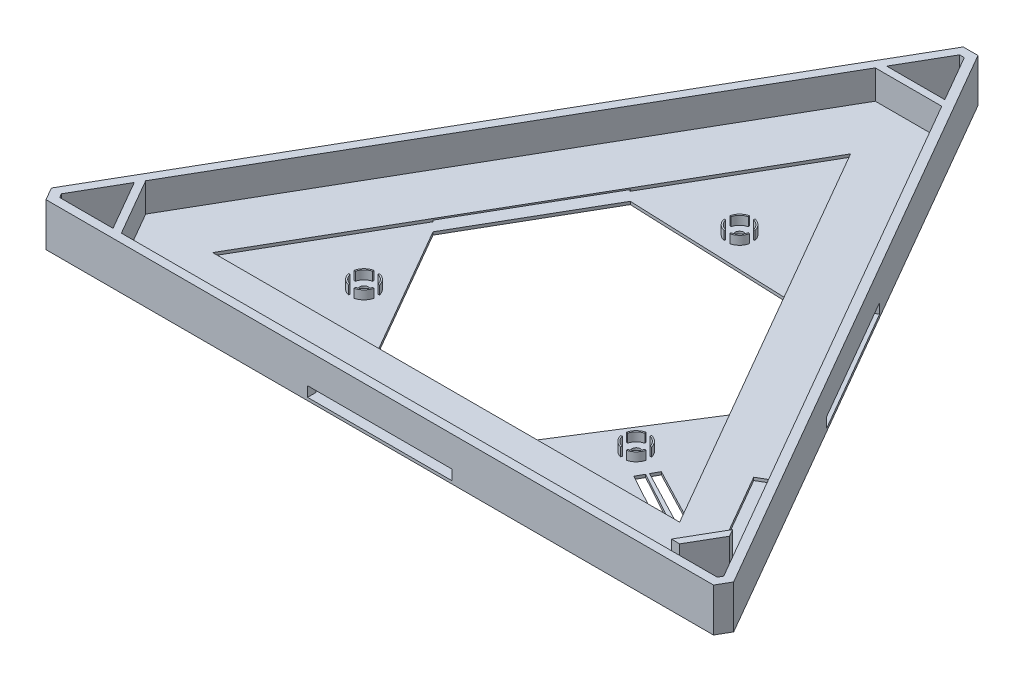
SolidWorks part; units mm, degrees
ref_plane "Front Plane" through (0, 0, 0) normal (0, 0, 1) x (1, 0, 0)
ref_plane "Top Plane" through (0, 0, 0) normal (0, 1, 0) x (1, 0, 0)
ref_plane "Right Plane" through (0, 0, 0) normal (1, 0, 0) x (0, 0, -1)
sketch "Sketch1" plane through (0, 0, 0) normal (0, 1, 0) x (1, 0, 0)
  line L0 (351.2729, 67.6655) -> (468.273, -134.9846)
  line L1 (347.2728, 67.6655) -> (347.2728, 65.1655) construction
  line L2 (409.773, -33.6595) -> (407.6079, -34.9095) construction
  line L3 (468.273, -134.9846) -> (464.2732, -141.9124)
  line L4 (230.2733, -141.9124) -> (464.2732, -141.9124)
  line L5 (230.2733, -141.9124) -> (226.2727, -134.9842)
  line L6 (226.2727, -134.9842) -> (343.2728, 67.6655)
  line L7 (353.4142, 63.9567) -> (351.2491, 62.7067) construction
  line L8 (347.2733, -141.9124) -> (347.2733, -139.4124) construction
  line L9 (231.7167, -139.4124) -> (462.8299, -139.4124)
  line L10 (284.7727, -33.6594) -> (286.9378, -34.9094) construction
  line L11 (344.7161, 65.1655) -> (349.8295, 65.1655)
  line L12 (465.3862, -134.9846) -> (349.8295, 65.1655)
  line L13 (466.2731, -138.4485) -> (464.1081, -137.1985) construction
  line L14 (462.8299, -139.4124) -> (465.3862, -134.9846)
  line L15 (229.1594, -134.9842) -> (344.7161, 65.1655)
  line L16 (229.1594, -134.9842) -> (231.7167, -139.4124)
  line L17 (286.9378, -34.9094) -> (287.3708, -35.1594) construction
  line L18 (230.438, -137.1983) -> (230.871, -136.9483) construction
  line L19 (232.0053, -138.9123) -> (229.7368, -134.9842)
  line L20 (343.2728, 67.6655) -> (351.2729, 67.6655)
  line L21 (345.0048, 64.6655) -> (229.7368, -134.9842)
  line L22 (349.5409, 64.6655) -> (345.0048, 64.6655)
  line L23 (249.0568, -126.4468) -> (246.8918, -127.697) construction
  line L24 (407.6079, -34.9095) -> (407.1749, -35.1595) construction
  line L26 (233.4463, -136.4089) -> (251.9226, -136.4093)
  line L27 (464.8089, -134.9846) -> (462.5412, -138.9123)
  line L28 (462.5412, -138.9123) -> (232.0053, -138.9123)
  line L29 (251.9226, -136.4093) -> (241.8609, -118.9847)
  line L30 (241.8609, -118.9847) -> (232.6236, -134.9842)
  line L31 (232.6236, -134.9842) -> (233.4463, -136.4089)
  line L33 (287.3708, -35.1594) -> (289.5359, -36.4094) construction
  line L34 (254.8093, -136.4089) -> (243.3042, -116.4848)
  line L35 (335.7675, 43.666) -> (243.3042, -116.4848)
  line L36 (358.7782, 43.666) -> (335.7675, 43.666)
  line L38 (289.5359, -36.4094) -> (306.8564, -46.4094) construction
  line L41 (461.939, -134.9846) -> (461.1164, -136.4093)
  line L42 (347.2688, -136.4172) -> (347.2688, -116.4172) construction
  line L43 (442.6021, -136.4093) -> (452.6999, -118.9847)
  line L44 (245.2636, -119.878) -> (249.0568, -126.4468) construction
  line L45 (452.6999, -118.9847) -> (461.939, -134.9846)
  line L48 (461.1164, -136.4093) -> (442.6021, -136.4093)
  line L49 (405.0134, -36.4027) -> (387.6936, -46.404) construction
  line L50 (439.7283, -128.9846) -> (405.0134, -128.9846)
  line L51 (357.3348, 46.166) -> (337.2109, 46.166)
  line L52 (337.2109, 46.166) -> (346.4484, 62.1659)
  line L53 (346.4484, 62.1659) -> (348.0966, 62.164)
  line L54 (348.0966, 62.164) -> (357.3348, 46.166)
  line L55 (228.273, -138.4483) -> (387.6936, -46.404) construction
  line L56 (347.2688, -116.4172) -> (347.2728, 43.666) construction
  line L57 (266.4391, -116.428) -> (428.1137, -116.4172)
  line L58 (347.2736, 23.6092) -> (428.1137, -116.4172)
  line L59 (266.4391, -116.428) -> (347.2736, 23.6092)
  line L60 (439.7283, -136.4254) -> (439.7283, -132.9254) construction
  line L61 (451.2487, -116.4715) -> (448.6507, -117.9717) construction
  line L62 (452.6999, -118.9847) -> (358.7782, 43.666)
  line L63 (442.6021, -136.4093) -> (254.8093, -136.4089)
  line L64 (441.749, -132.9254) -> (444.621, -132.9254)
  line L65 (448.6507, -117.9717) -> (450.9647, -121.979) construction
  line L66 (449.5167, -119.4714) -> (450.9647, -121.979)
  line L67 (441.749, -132.9254) -> (449.5167, -119.4714)
  line L68 (450.9647, -121.979) -> (444.621, -132.9254)
  line L69 (405.0134, -128.9846) -> (405.0134, -134.9846)
  line L70 (444.9234, -120.3654) -> (427.4553, -90.1147)
  line L73 (405.0134, -134.9846) -> (439.7283, -134.9846)
  line L76 (439.7283, -134.9846) -> (439.7283, -128.9846)
  line L77 (432.6513, -87.1143) -> (427.4553, -90.1147)
  line L78 (405.0134, -134.9846) -> (433.4739, -85.6896) construction
  line L81 (432.6513, -87.1143) -> (450.1194, -117.365)
  line L83 (450.1194, -117.365) -> (444.9234, -120.3654)
  point P13 (407.6079, -34.9095)
  point P20 (464.1081, -137.1985)
  point P23 (347.2733, -139.4124)
  point P25 (347.2732, -141.9124)
  point P27 (347.2728, 65.1655)
  point P31 (286.9378, -34.9094)
  point P37 (287.3708, -35.1594)
  point P39 (230.871, -136.9483)
  point P41 (347.2728, 64.6655)
  point P45 (407.1749, -35.1595)
  point P50 (246.8918, -127.697)
  point P56 (289.5359, -36.4094)
  point P58 (249.0568, -126.4468)
  point P60 (347.2728, 43.666)
  point P62 (345.0048, -136.4089)
  point P64 (445.4885, -126.4485)
  point P71 (447.651, -127.697)
  point P77 (347.2728, 46.166)
  point P84 (347.2688, -116.4172)
  point P87 (387.6936, -46.404)
  point P89 (306.8564, -46.4094)
  point P100 (405.0134, -36.4027)
  dimension "D1" = 2.5
  dimension "D2" = 2.5
  dimension "D3" = 2.5
  dimension "D4" = 2.5
  dimension "D5" = 2.5
  dimension "D6" = 2.5
  dimension "D7" = 0.5
  dimension "D8" = 0.5
  dimension "D9" = 0.5
  dimension "D10" = 2.5
  dimension "D11" = 2.5
  dimension "D12" = 20
  dimension "D13" = 20
  dimension "D14" = 20
  dimension "D15" = 3.5
  dimension "D16" = 3
  dimension "D17" = 6
  dimension "D18" = 6
extrude "Boss-Extrude1" add sketch "Sketch1" along normal blind 1 contours L36 L35 L34 L57 L59 L58 region at (251.4484, 0, 125.0658)
extrude "Boss-Extrude2" add sketch "Sketch1<9>" along normal blind 11 contours L28 L27 L22 L21 L19 L31 L30 L29 L26 L34 L35 L36 L41 L48 L43 L45 L53 L54 L51 L52 | L68 L64 L67 L66 region at (230.7087, 0, 137.042)
sketch "Sketch1<9>" plane through (0, 0, 0) normal (0, 1, 0) x (1, 0, 0) same geometry as "Sketch1"
extrude "Boss-Extrude3" add sketch "Sketch1<10>" along normal blind 5 and the other way blind 3 contours L28 L27 L22 L21 L19 L31 L30 L29 L26 L34 L35 L36 L41 L48 L43 L45 L53 L54 L51 L52 | L68 L64 L67 L66 region at (230.7087, 0, 137.042)
sketch "Sketch1<10>" plane through (0, 0, 0) normal (0, 1, 0) x (1, 0, 0) same geometry as "Sketch1"
sketch "Sketch3" plane through (290.5896, 0, -167.772) normal (0.866, 0, -0.5) x (-0.5, 0, -0.866)
  line L1 (-261.593, -6.5) -> (-211.593, -6.5)
  line L2 (-261.593, -6.5) -> (-261.593, 0.5)
  line L3 (-261.593, 0.5) -> (-211.593, 0.5)
  line L4 (-211.593, -6.5) -> (-211.593, 0.5)
  line L5 (-261.593, -6.5) -> (-211.593, 0.5) construction
  line L6 (-261.593, 0.5) -> (-211.593, -6.5) construction
  point P0 (-236.593, -3)
  dimension "D1" = 50
  dimension "D2" = 7
extrude "Cut-Extrude3" cut sketch "Sketch3" against normal blind 25
sketch "Sketch5" plane through (0, 0, 139.4124) normal (0, 0, 1) x (1, 0, 0)
  line L0 (231.7167, -3) -> (462.8299, -3) construction
  line L1 (322.2733, -6.5) -> (372.2733, -6.5)
  line L2 (322.2733, -6.5) -> (322.2733, 0.5)
  line L3 (322.2733, 0.5) -> (372.2733, 0.5)
  line L4 (372.2733, -6.5) -> (372.2733, 0.5)
  line L5 (322.2733, -6.5) -> (372.2733, 0.5) construction
  line L6 (322.2733, 0.5) -> (372.2733, -6.5) construction
  point P0 (347.2733, -3)
  dimension "D1" = 50
  dimension "D2" = 7
extrude "Cut-Extrude4" cut sketch "Sketch5" against normal blind 25
sketch "Sketch6" plane through (230.3194, 0, 132.9752) normal (-0.866, 0, -0.5) x (-0.5, 0, 0.866)
  line L0 (2.3199, -3) -> (-228.7932, -3) construction
  line L1 (-138.2367, -6.5) -> (-88.2367, -6.5)
  line L2 (-138.2367, -6.5) -> (-138.2367, 0.5)
  line L3 (-138.2367, 0.5) -> (-88.2367, 0.5)
  line L4 (-88.2367, -6.5) -> (-88.2367, 0.5)
  line L5 (-138.2367, -6.5) -> (-88.2367, 0.5) construction
  line L6 (-138.2367, 0.5) -> (-88.2367, -6.5) construction
  point P0 (-113.2367, -3)
  dimension "D1" = 50
  dimension "D2" = 7
extrude "Cut-Extrude5" cut sketch "Sketch6" against normal blind 25
sketch "Sketch8" plane through (0, -3, 0) normal (0, -1, 0) x (1, 0, 0)
  line L1 (349.8295, -65.1655) -> (465.3862, 134.9846)
  line L2 (465.3862, 134.9846) -> (462.8299, 139.4124)
  line L4 (444.621, 132.9254) -> (450.9647, 121.979)
  line L6 (462.8299, 139.4124) -> (231.7167, 139.4124)
  line L9 (452.6999, 118.9847) -> (461.939, 134.9846)
  line L12 (461.939, 134.9846) -> (461.1164, 136.4093)
  line L15 (450.9647, 121.979) -> (444.621, 132.9254) construction
  line L17 (461.1164, 136.4093) -> (442.6021, 136.4093)
  line L19 (322.2733, 116.4243) -> (294.3582, 68.0611)
  line L20 (294.3582, 68.0611) -> (319.3545, 24.7577)
  line L21 (319.3545, 24.7577) -> (376.4737, 26.9694)
  line L22 (376.4737, 26.9694) -> (401.4727, 70.2712)
  line L23 (401.4727, 70.2712) -> (372.2733, 116.4209)
  line L24 (372.2733, 116.4209) -> (322.2733, 116.4243)
  line L25 (386.873, 93.3461) -> (395.3235, 98.6928) construction
  line L30 (308.3157, 92.2427) -> (299.6549, 97.2417) construction
  line L31 (347.9141, 25.8635) -> (348.3013, 15.8635) construction
  line L37 (231.7167, 139.4124) -> (229.1594, 134.9842)
  line L39 (233.4463, 136.4089) -> (251.9226, 136.4093)
  line L40 (251.9226, 136.4093) -> (241.8609, 118.9847)
  line L41 (241.8609, 118.9847) -> (232.6236, 134.9842)
  line L42 (232.6236, 134.9842) -> (233.4463, 136.4089)
  line L43 (349.8295, -65.1655) -> (344.7161, -65.1655)
  line L44 (344.7161, -65.1655) -> (229.1594, 134.9842)
  line L45 (337.2109, -46.166) -> (357.3348, -46.166)
  line L46 (357.3348, -46.166) -> (348.0966, -62.164)
  line L47 (348.0966, -62.164) -> (346.4484, -62.1659)
  line L48 (346.4484, -62.1659) -> (337.2109, -46.166)
  line L53 (442.6021, 136.4093) -> (439.0196, 136.4093)
  line L54 (439.0196, 136.4093) -> (420.3794, 116.4177)
  line L55 (424.5493, 110.2432) -> (451.8713, 117.5496)
  line L59 (372.2733, 116.4209) -> (428.1137, 116.4172) construction
  line L60 (401.4727, 70.2712) -> (428.1137, 116.4172) construction
  line L61 (451.8713, 117.5496) -> (452.6999, 118.9847)
  line L62 (426.6202, 116.4173) -> (441.749, 132.9254)
  line L63 (441.749, 132.9254) -> (444.621, 132.9254)
  line L65 (427.3476, 115.0902) -> (449.5167, 119.4714)
  line L66 (449.5167, 119.4714) -> (450.9647, 121.979)
  line L67 (449.5167, 119.4714) -> (450.9647, 121.979) construction
  line L68 (441.749, 132.9254) -> (449.5167, 119.4714) construction
  line L70 (403.8523, 103.9378) -> (426.6202, 116.4173)
  line L72 (404.333, 103.0609) -> (427.3476, 115.0902)
  line L74 (442.6021, 136.4093) -> (372.2733, 136.4092) construction
  line L75 (461.939, 134.9846) -> (418.7954, 60.2699) construction
  line L76 (420.3794, 116.4177) -> (402.4104, 106.5685)
  line L77 (402.4104, 106.5685) -> (403.8523, 103.9378)
  line L78 (404.333, 103.0609) -> (405.7749, 100.4301)
  line L79 (405.7749, 100.4301) -> (424.5493, 110.2432)
  line L80 (395.3235, 98.6928) -> (447.7929, 127.4522) construction
  line L81 (395.3235, 98.6928) -> (404.0927, 103.4993) construction
  line L82 (404.0927, 103.4993) -> (404.333, 103.0609) construction
  line L83 (404.0927, 103.4993) -> (403.8523, 103.9378) construction
  line L84 (403.8523, 103.9378) -> (402.4104, 106.5685) construction
  line L85 (404.333, 103.0609) -> (405.7749, 100.4301) construction
  line L86 (402.4104, 106.5685) -> (420.3794, 116.4177) construction
  line L87 (405.7749, 100.4301) -> (424.5493, 110.2432) construction
  line L88 (404.333, 103.0609) -> (427.842, 115.9466) construction
  line L89 (403.8523, 103.9378) -> (426.6202, 116.4173) construction
  line L90 (426.6202, 116.4173) -> (427.3476, 115.0902) construction
  line L91 (420.3794, 116.4177) -> (424.1464, 109.5452) construction
  circle A0 centre (395.3235, 98.6928) radius 1.5
  circle A1 centre (348.3013, 15.8635) radius 1.5
  circle A2 centre (299.6549, 97.2417) radius 1.5
  point P4 (424.5493, 110.2432)
  dimension "D6" = 3
  dimension "D7" = 3
  dimension "D8" = 3
  dimension "D1" = 10
  dimension "D2" = 0.5
  dimension "D3" = 10
  dimension "D4" = 10
  dimension "D5" = 10
  dimension "D9" = 0.5
  dimension "D10" = 3
  dimension "D11" = 3
extrude "Boss-Extrude5" add sketch "Sketch8" along normal blind 1
sketch "Sketch12" plane through (0, -3, 0) normal (0, 1, 0) x (1, 0, 0)
  line L0 (348.3013, -11.8635) -> (348.3013, -11.3635) construction
  line L1 (348.3013, -11.3635) -> (349.2951, -11.4746) construction
  line L2 (349.2951, -11.4746) -> (349.1847, -11.9623)
  line L3 (348.3013, -11.3635) -> (347.3075, -11.4746) construction
  line L4 (347.3075, -11.4746) -> (347.4179, -11.9623)
  line L5 (352.3013, -15.8635) -> (352.8013, -15.8635) construction
  line L6 (344.3013, -15.8635) -> (343.8013, -15.8635) construction
  line L7 (348.3013, -19.8635) -> (348.3013, -20.3635) construction
  line L8 (352.8013, -15.8635) -> (352.6902, -14.8697) construction
  line L9 (352.8013, -15.8635) -> (352.6902, -16.8573) construction
  line L10 (343.8013, -15.8635) -> (343.9124, -14.8697) construction
  line L11 (343.8013, -15.8635) -> (343.9124, -16.8573) construction
  line L12 (348.3013, -20.3635) -> (349.2951, -20.2524) construction
  line L13 (348.3013, -20.3635) -> (347.3075, -20.2524) construction
  line L14 (343.9124, -14.8697) -> (348.3013, -15.8635) construction
  line L15 (348.3013, -15.8635) -> (352.6902, -14.8697) construction
  line L16 (343.9124, -16.8573) -> (348.3013, -15.8635) construction
  line L17 (348.3013, -15.8635) -> (352.6902, -16.8573) construction
  line L18 (347.3075, -20.2524) -> (348.3013, -15.8635) construction
  line L19 (348.3013, -15.8635) -> (349.2951, -20.2524) construction
  line L20 (343.9124, -14.8697) -> (344.4001, -14.9801)
  line L21 (343.9124, -16.8573) -> (344.4001, -16.7469)
  line L22 (347.3075, -20.2524) -> (347.4179, -19.7648)
  line L23 (349.2951, -20.2524) -> (349.1847, -19.7648)
  line L24 (352.6902, -14.8697) -> (352.2025, -14.9801)
  line L25 (352.6902, -16.8573) -> (352.2025, -16.7469)
  line L26 (395.3235, -94.1928) -> (395.3235, -98.6928) construction
  line L27 (395.3235, -98.6928) -> (390.8235, -98.6928) construction
  line L28 (390.8235, -98.6928) -> (390.9347, -97.699) construction
  line L29 (399.8235, -98.6928) -> (395.3235, -98.6928) construction
  line L30 (395.3235, -98.6928) -> (395.3235, -103.1928) construction
  line L31 (395.3235, -103.1928) -> (396.3173, -103.0817) construction
  line L32 (395.3235, -94.1928) -> (396.3173, -94.3039) construction
  line L33 (395.3235, -94.1928) -> (394.3297, -94.3039) construction
  line L34 (399.7124, -97.699) -> (399.8235, -98.6928) construction
  line L35 (399.8235, -98.6928) -> (399.7124, -99.6866) construction
  line L36 (390.9347, -99.6866) -> (390.8235, -98.6928) construction
  line L37 (394.3297, -103.0817) -> (395.3235, -103.1928) construction
  line L38 (394.3297, -94.3039) -> (395.3235, -98.6928) construction
  line L39 (395.3235, -98.6928) -> (396.3173, -94.3039) construction
  line L40 (390.9347, -99.6866) -> (395.3235, -98.6928) construction
  line L41 (395.3235, -98.6928) -> (390.9347, -97.699) construction
  line L42 (399.7124, -97.699) -> (395.3235, -98.6928) construction
  line L43 (395.3235, -98.6928) -> (399.7124, -99.6866) construction
  line L44 (394.3297, -103.0817) -> (395.3235, -98.6928) construction
  line L45 (395.3235, -98.6928) -> (396.3173, -103.0817) construction
  line L46 (394.3297, -94.3039) -> (394.4402, -94.7916)
  line L47 (396.3173, -94.3039) -> (396.2069, -94.7916)
  line L48 (399.7124, -97.699) -> (399.2248, -97.8094)
  line L49 (399.7124, -99.6866) -> (399.2248, -99.5762)
  line L50 (396.3173, -103.0817) -> (396.2069, -102.5941)
  line L51 (394.3297, -103.0817) -> (394.4402, -102.5941)
  line L52 (390.9347, -99.6866) -> (391.4223, -99.5762)
  line L53 (390.9347, -97.699) -> (391.4248, -97.7985)
  line L54 (299.6549, -92.7417) -> (299.6549, -97.2417) construction
  line L55 (299.6549, -97.2417) -> (304.1549, -97.2417) construction
  line L56 (299.6549, -101.7417) -> (299.6549, -97.2417) construction
  line L57 (299.6549, -97.2417) -> (295.1549, -97.2417) construction
  line L58 (299.6549, -97.2417) -> (298.6611, -92.8528) construction
  line L59 (298.6611, -92.8528) -> (299.6549, -92.7417) construction
  line L60 (299.6549, -92.7417) -> (300.6487, -92.8528) construction
  line L61 (300.6487, -92.8528) -> (299.6549, -97.2417) construction
  line L62 (299.6549, -97.2417) -> (304.0438, -96.2479) construction
  line L63 (304.0438, -96.2479) -> (304.1549, -97.2417) construction
  line L64 (304.1549, -97.2417) -> (304.0438, -98.2355) construction
  line L65 (304.0438, -98.2355) -> (299.6549, -97.2417) construction
  line L66 (299.6549, -97.2417) -> (300.6487, -101.6306) construction
  line L67 (300.6487, -101.6306) -> (299.6549, -101.7417) construction
  line L68 (299.6549, -101.7417) -> (298.6611, -101.6306) construction
  line L69 (298.6611, -101.6306) -> (299.6549, -97.2417) construction
  line L70 (299.6549, -97.2417) -> (295.266, -98.2355) construction
  line L71 (295.266, -98.2355) -> (295.1549, -97.2417) construction
  line L72 (295.1549, -97.2417) -> (295.266, -96.2479) construction
  line L73 (295.266, -96.2479) -> (299.6549, -97.2417) construction
  line L74 (295.266, -96.2479) -> (295.7537, -96.3583)
  line L75 (295.266, -98.2355) -> (295.7537, -98.1251)
  line L76 (298.6611, -101.6306) -> (298.7715, -101.1429)
  line L77 (300.6487, -101.6306) -> (300.5383, -101.1429)
  line L78 (304.0438, -98.2355) -> (303.5561, -98.1251)
  line L79 (304.0438, -96.2479) -> (303.5561, -96.3583)
  line L80 (300.6487, -92.8528) -> (300.5383, -93.3404)
  line L81 (298.6611, -92.8528) -> (298.7715, -93.3404)
  circle A0 centre (348.3013, -15.8635) radius 4.5
  circle A1 centre (395.3235, -98.6928) radius 4.5
  circle A2 centre (299.6549, -97.2417) radius 4.5
  circle A3 centre (348.3013, -15.8635) radius 4
  circle A4 centre (395.3235, -98.6928) radius 4
  circle A5 centre (299.6549, -97.2417) radius 4
  dimension "D1" = 9
  dimension "D2" = 9
  dimension "D3" = 9
  dimension "D4" = 8
  dimension "D5" = 8
  dimension "D6" = 8
  dimension "D7" = 1
  dimension "D8" = 1
  dimension "D9" = 1
  dimension "D10" = 1
  dimension "D11" = 1
  dimension "D12" = 1
  dimension "D13" = 1
  dimension "D14" = 1
  dimension "D15" = 1
  dimension "D16" = 1
  dimension "D17" = 1
  dimension "D18" = 1
  dimension "D19" = 1
  dimension "D20" = 1
  dimension "D21" = 1
  dimension "D22" = 1
  dimension "D23" = 1
  dimension "D24" = 1
  dimension "D25" = 1
  dimension "D26" = 1
  dimension "D27" = 1
  dimension "D28" = 1
  dimension "D29" = 1
  dimension "D30" = 1
extrude "Boss-Extrude10" add sketch "Sketch12" along normal blind 3 contours A3 L4 A0 L20 | A3 L24 A0 L2 | A3 L23 A0 L25 | A3 L21 A0 L22 | A4 L46 A1 L53 | A4 L48 A1 L47 | A4 L50 A1 L49 | A4 L52 A1 L51 | A5 L81 A2 L74 | A5 L79 A2 L80 | A5 L77 A2 L78 | A5 L75 A2 L76 region at (351.1537, -3, 13.0111) region at (345.4489, -3, 13.0111) region at (351.1537, -3, 18.7159) region at (345.4489, -3, 18.7159) region at (392.4726, -3, 95.8382) region at (398.1759, -3, 95.8404) region at (392.4712, -3, 101.5452) region at (398.1759, -3, 101.5452) region at (296.8025, -3, 94.3893) region at (296.8025, -3, 100.0941) region at (302.5073, -3, 94.3893) region at (302.5073, -3, 100.0941)
